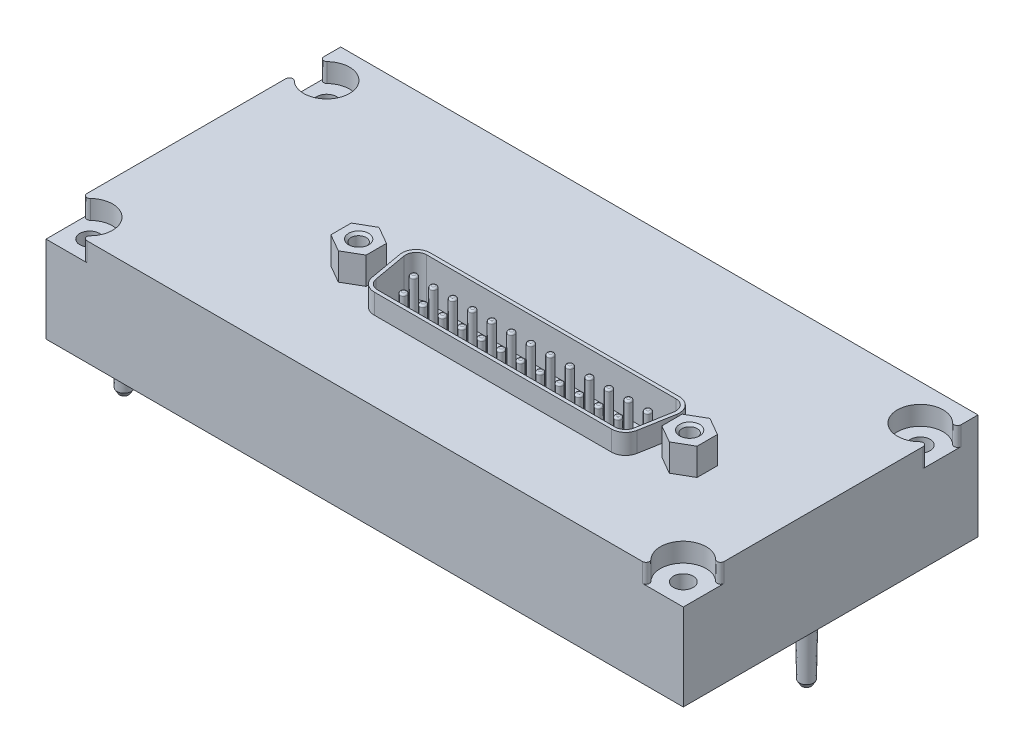
SolidWorks part; units mm, degrees
ref_plane "Ebene vorne" through (0, 0, 0) normal (0, 0, 1) x (1, 0, 0)
ref_plane "Ebene oben" through (0, 0, 0) normal (0, 1, 0) x (1, 0, 0)
ref_plane "Ebene rechts" through (0, 0, 0) normal (1, 0, 0) x (0, 0, -1)
sketch "Skizze1" plane through (0, 0, 0) normal (0, 1, 0) x (1, 0, 0)
  line L0 (-34.25, 15.25) -> (-34.25, -26.6)
  line L1 (-34.25, -26.6) -> (56.25, -26.6)
  line L2 (56.25, -26.6) -> (56.25, 15.25)
  line L3 (56.25, 15.25) -> (-34.25, 15.25)
  circle A0 centre (53.15, -23.5) radius 1.4
  circle A1 centre (53.15, 10.15) radius 1.4
  circle A2 centre (-31.15, -23.5) radius 1.4
  circle A3 centre (-31.15, 10.15) radius 1.4
extrude "Aufsatz-Linear austragen1" add sketch "Skizze1" along normal blind 15
ref_plane "Ebene1" through (0, 15, 0) normal (0, 1, 0) x (1, 0, 0)
sketch "Skizze2" plane through (0, 15, 0) normal (0, 1, 0) x (1, 0, 0)
  line L0 (-45, 30) -> (-45, -40)
  line L1 (-45, -40) -> (65, -40)
  line L2 (65, -40) -> (65, 30)
  line L3 (65, 30) -> (-45, 30)
  line L4 (-34.25, 7.4477) -> (-34.25, -20.7977)
  line L5 (-28.4477, -26.6) -> (50.4477, -26.6)
  line L6 (56.25, -20.7977) -> (56.25, 7.4477)
  line L7 (56.25, 12.8523) -> (56.25, 15.25)
  line L8 (56.25, 15.25) -> (-34.25, 15.25)
  line L9 (-34.25, 15.25) -> (-34.25, 12.8523)
  arc A0 (-34.25, 12.8523) -> (-33.4033, 12.492) centre (-33.75, 12.8523) ccw
  arc A1 (-33.4033, 12.492) -> (-33.4033, 7.808) centre (-31.15, 10.15) cw
  arc A2 (-33.4033, 7.808) -> (-34.25, 7.4477) centre (-33.75, 7.4477) ccw
  arc A3 (-34.25, -20.7977) -> (-33.4033, -21.158) centre (-33.75, -20.7977) ccw
  arc A4 (-33.4033, -21.158) -> (-28.808, -25.7533) centre (-31.15, -23.5) cw
  arc A5 (-28.808, -25.7533) -> (-28.4477, -26.6) centre (-28.4477, -26.1) ccw
  arc A6 (50.4477, -26.6) -> (50.808, -25.7533) centre (50.4477, -26.1) ccw
  arc A7 (50.808, -25.7533) -> (55.4033, -21.158) centre (53.15, -23.5) cw
  arc A8 (55.4033, -21.158) -> (56.25, -20.7977) centre (55.75, -20.7977) ccw
  arc A9 (56.25, 7.4477) -> (55.4033, 7.808) centre (55.75, 7.4477) ccw
  arc A10 (55.4033, 7.808) -> (55.4033, 12.492) centre (53.15, 10.15) cw
  arc A11 (55.4033, 12.492) -> (56.25, 12.8523) centre (55.75, 12.8523) ccw
extrude "Schnitt-Linear austragen1" cut sketch "Skizze2" against normal blind 2.7
ref_plane "Ebene2" through (0, 0, 6) normal (0, 0, 1) x (1, 0, 0)
sketch "Skizze3" plane through (0, 0, 6) normal (0, 0, 1) x (1, 0, 0)
  line L0 (53.15, 0) -> (54.3, 0)
  line L1 (54.3, 0) -> (54.15, -8.4)
  line L2 (54.15, -8.4) -> (53.8, -9)
  line L3 (53.8, -9) -> (53.15, -9)
  line L4 (53.15, -9) -> (53.15, 0)
  line L5 (53.15, -9) -> (53.15, 0) construction
revolve "Rotation1" add sketch "Skizze3" angle 360 about L5 reverse direction yes
ref_plane "Ebene3" through (0, 0, -5.25) normal (0, 0, 1) x (1, 0, 0)
sketch "Skizze4" plane through (0, 0, -5.25) normal (0, 0, 1) x (1, 0, 0)
  line L0 (-31.15, 0) -> (-30, 0)
  line L1 (-30, 0) -> (-30.15, -8.4)
  line L2 (-30.15, -8.4) -> (-30.5, -9)
  line L3 (-30.5, -9) -> (-31.15, -9)
  line L4 (-31.15, -9) -> (-31.15, 0)
  line L5 (-31.15, -9) -> (-31.15, 0) construction
revolve "Rotation2" add sketch "Skizze4" angle 360 about L5 reverse direction yes
ref_plane "Ebene4" through (0, 0, 18.6) normal (0, 0, 1) x (1, 0, 0)
sketch "Skizze5" plane through (0, 0, 18.6) normal (0, 0, 1) x (1, 0, 0)
  line L0 (-31.15, 0) -> (-30, 0)
  line L1 (-30, 0) -> (-30.15, -8.4)
  line L2 (-30.15, -8.4) -> (-30.5, -9)
  line L3 (-30.5, -9) -> (-31.15, -9)
  line L4 (-31.15, -9) -> (-31.15, 0)
  line L5 (-31.15, -9) -> (-31.15, 0) construction
revolve "Rotation3" add sketch "Skizze5" angle 360 about L5 reverse direction yes
sketch "Skizze6" plane through (0, 15, 0) normal (0, 1, 0) x (1, 0, 0)
  line L0 (39, -12.3934) -> (41.5, -13.8368)
  line L1 (41.5, -13.8368) -> (44, -12.3934)
  line L2 (44, -12.3934) -> (44, -9.5066)
  line L3 (44, -9.5066) -> (41.5, -8.0632)
  line L4 (41.5, -8.0632) -> (39, -9.5066)
  line L5 (39, -9.5066) -> (39, -12.3934)
extrude "Aufsatz-Linear austragen2" add sketch "Skizze6" along normal blind 3.85
sketch "Skizze7" plane through (0, 15, 0) normal (0, 1, 0) x (1, 0, 0)
  line L0 (-8, -12.3934) -> (-5.5, -13.8368)
  line L1 (-5.5, -13.8368) -> (-3, -12.3934)
  line L2 (-3, -12.3934) -> (-3, -9.5066)
  line L3 (-3, -9.5066) -> (-5.5, -8.0632)
  line L4 (-5.5, -8.0632) -> (-8, -9.5066)
  line L5 (-8, -9.5066) -> (-8, -12.3934)
extrude "Aufsatz-Linear austragen3" add sketch "Skizze7" along normal blind 3.85
sketch "Skizze8" plane through (0, 15, 0) normal (0, 1, 0) x (1, 0, 0)
  line L0 (-1.2096, -8.8105) -> (-0.3632, -13.6105)
  line L1 (1.114, -14.85) -> (34.806, -14.85)
  line L2 (36.2832, -13.6105) -> (37.1296, -8.8105)
  line L3 (35.6524, -7.05) -> (0.2676, -7.05)
  arc A0 (0.2676, -7.05) -> (-1.2096, -8.8105) centre (0.2676, -8.55) ccw
  arc A1 (-0.3632, -13.6105) -> (1.114, -14.85) centre (1.114, -13.35) ccw
  arc A2 (34.806, -14.85) -> (36.2832, -13.6105) centre (34.806, -13.35) ccw
  arc A3 (37.1296, -8.8105) -> (35.6524, -7.05) centre (35.6524, -8.55) ccw
extrude "Schnitt-Linear austragen2" cut sketch "Skizze8" against normal blind 3
sketch "Skizze9" plane through (0, 15, 0) normal (0, 1, 0) x (1, 0, 0)
  line L0 (-1.702, -8.8973) -> (-0.8556, -13.6973)
  line L1 (1.114, -15.35) -> (34.806, -15.35)
  line L2 (36.7756, -13.6973) -> (37.622, -8.8973)
  line L3 (35.6524, -6.55) -> (0.2676, -6.55)
  line L4 (-1.2096, -8.8105) -> (-0.3632, -13.6105)
  line L5 (1.114, -14.85) -> (34.806, -14.85)
  line L6 (36.2832, -13.6105) -> (37.1296, -8.8105)
  line L7 (35.6524, -7.05) -> (0.2676, -7.05)
  arc A0 (0.2676, -6.55) -> (-1.702, -8.8973) centre (0.2676, -8.55) ccw
  arc A1 (-0.8556, -13.6973) -> (1.114, -15.35) centre (1.114, -13.35) ccw
  arc A2 (34.806, -15.35) -> (36.7756, -13.6973) centre (34.806, -13.35) ccw
  arc A3 (37.622, -8.8973) -> (35.6524, -6.55) centre (35.6524, -8.55) ccw
  arc A4 (0.2676, -7.05) -> (-1.2096, -8.8105) centre (0.2676, -8.55) ccw
  arc A5 (-0.3632, -13.6105) -> (1.114, -14.85) centre (1.114, -13.35) ccw
  arc A6 (34.806, -14.85) -> (36.2832, -13.6105) centre (34.806, -13.35) ccw
  arc A7 (37.1296, -8.8105) -> (35.6524, -7.05) centre (35.6524, -8.55) ccw
extrude "Aufsatz-Linear austragen4" add sketch "Skizze9" along normal blind 2.84
ref_plane "Ebene5" through (0, 0, 10.95) normal (0, 0, 1) x (1, 0, 0)
sketch "Skizze10" plane through (0, 0, 10.95) normal (0, 0, 1) x (1, 0, 0)
  line L0 (41.5, 18.85) -> (42.9224, 18.85)
  line L1 (42.9224, 18.85) -> (42.5782, 18.5058)
  line L2 (42.5782, 18.5058) -> (42.5782, 14.4725)
  line L3 (42.5782, 14.4725) -> (41.5, 13.85)
  line L4 (41.5, 13.85) -> (41.5, 18.85)
  line L5 (41.5, 13.85) -> (41.5, 18.85) construction
revolve "Schnitt-Rotation1" cut sketch "Skizze10" angle 360 about L5 reverse direction yes
cosmetic thread "Gewindedarstellung1" parameters "D1"=3.4, "D2"=2.8448
sketch "Skizze11" plane through (0, 0, 10.95) normal (0, 0, 1) x (1, 0, 0)
  line L0 (-5.5, 18.85) -> (-4.0776, 18.85)
  line L1 (-4.0776, 18.85) -> (-4.4218, 18.5058)
  line L2 (-4.4218, 18.5058) -> (-4.4218, 14.4725)
  line L3 (-4.4218, 14.4725) -> (-5.5, 13.85)
  line L4 (-5.5, 13.85) -> (-5.5, 18.85)
  line L5 (-5.5, 13.85) -> (-5.5, 18.85) construction
revolve "Schnitt-Rotation2" cut sketch "Skizze11" angle 360 about L5 reverse direction yes
cosmetic thread "Gewindedarstellung2" parameters "D1"=3.4, "D2"=2.8448
ref_plane "Ebene6" through (0, 0, 12.37) normal (0, 0, 1) x (1, 0, 0)
sketch "Skizze12" plane through (0, 0, 12.37) normal (0, 0, 1) x (1, 0, 0)
  line L0 (2.305, 17) -> (2.53, 17)
  line L1 (2.78, 16.75) -> (2.78, 12)
  line L2 (2.78, 12) -> (2.305, 12)
  line L3 (2.305, 12) -> (2.305, 17)
  line L4 (2.305, 12) -> (2.305, 17) construction
  arc A0 (2.53, 17) -> (2.78, 16.75) centre (2.53, 16.75) cw
revolve "Rotation4" add sketch "Skizze12" angle 360 about L4 reverse direction yes
ref_plane "Ebene7" through (0, 12, 0) normal (0, 1, 0) x (1, 0, 0)
sketch "Skizze13" plane through (0, 12, 0) normal (0, 1, 0) x (1, 0, 0)
  line L0 (2.305, -12.37) -> (32.775, -12.37)
pattern_linear "Lineares Muster1" count 12 spacing 2.77 along (1, 0, 0) of "Rotation4"
ref_plane "Ebene8" through (0, 0, 9.53) normal (0, 0, 1) x (1, 0, 0)
sketch "Skizze14" plane through (0, 0, 9.53) normal (0, 0, 1) x (1, 0, 0)
  line L0 (0.92, 17) -> (1.145, 17)
  line L1 (1.395, 16.75) -> (1.395, 12)
  line L2 (1.395, 12) -> (0.92, 12)
  line L3 (0.92, 12) -> (0.92, 17)
  line L4 (0.92, 12) -> (0.92, 17) construction
  arc A0 (1.145, 17) -> (1.395, 16.75) centre (1.145, 16.75) cw
revolve "Rotation5" add sketch "Skizze14" angle 360 about L4 reverse direction yes
sketch "Skizze15" plane through (0, 12, 0) normal (0, 1, 0) x (1, 0, 0)
  line L0 (0.92, -9.53) -> (34.16, -9.53)
pattern_linear "Lineares Muster2" count 13 spacing 2.77 along (1, 0, 0) of "Rotation5"
ref_plane "Ebene9" through (0, 0, 10.95) normal (0, 0, 1) x (1, 0, 0)
ref_plane "Ebene10" through (0, 12.3, 0) normal (0, 1, 0) x (1, 0, 0)
ref_plane "Ebene11" through (0, 18.85, 0) normal (0, 1, 0) x (1, 0, 0)
ref_plane "ANBAU XY" through (0, 0, 0) normal (0, 1, 0) x (1, 0, 0)
ref_plane "ANBAU XZ" through (0, 0, 6) normal (0, 0, -1) x (-1, 0, 0)
ref_plane "ANBAU YZ" through (53.15, 0, 0) normal (-1, 0, 0) x (0, 0, 1)
ref_axis "ANBAU X" through (80.9, 0, 6) along (-1, 0, 0)
ref_axis "ANBAU Y" through (53.15, 0, -50) along (0, 0, 1)
ref_axis "ANBAU Z" through (53.15, 50, 6) along (0, -1, 0)
sketch3d "ANBAU"
  point P0 (53.15, 0, 6)
ref_plane "EZ XY" through (0, 18.85, 0) normal (0, -1, 0) x (-1, 0, 0)
ref_plane "EZ XZ" through (0, 0, 10.95) normal (0, 0, -1) x (-1, 0, 0)
ref_plane "EZ YZ" through (-5.5, 0, 0) normal (1, 0, 0) x (0, 0, -1)
ref_axis "EZ X" through (-80.9, 18.85, 10.95) along (1, 0, 0)
ref_axis "EZ Y" through (-5.5, 18.85, -50) along (0, 0, 1)
ref_axis "EZ Z" through (-5.5, -50, 10.95) along (0, 1, 0)
sketch3d "EZ"
  point P0 (-5.5, 18.85, 10.95)
ref_plane "SCREW 1 XY" through (0, 12.3, 0) normal (0, -1, 0) x (-1, 0, 0)
ref_plane "SCREW 1 XZ" through (0, 0, 23.5) normal (0, 0, -1) x (-1, 0, 0)
ref_plane "SCREW 1 YZ" through (-31.15, 0, 0) normal (1, 0, 0) x (0, 0, -1)
ref_axis "SCREW 1 X" through (-80.9, 12.3, 23.5) along (1, 0, 0)
ref_axis "SCREW 1 Y" through (-31.15, 12.3, -50) along (0, 0, 1)
ref_axis "SCREW 1 Z" through (-31.15, -50, 23.5) along (0, 1, 0)
sketch3d "SCREW 1"
  point P0 (-31.15, 12.3, 23.5)
ref_plane "SCREW 2 XY" through (0, 12.3, 0) normal (0, -1, 0) x (-1, 0, 0)
ref_plane "SCREW 2 XZ" through (0, 0, 23.5) normal (0, 0, -1) x (-1, 0, 0)
ref_plane "SCREW 2 YZ" through (53.15, 0, 0) normal (1, 0, 0) x (0, 0, -1)
ref_axis "SCREW 2 X" through (-80.9, 12.3, 23.5) along (1, 0, 0)
ref_axis "SCREW 2 Y" through (53.15, 12.3, -50) along (0, 0, 1)
ref_axis "SCREW 2 Z" through (53.15, -50, 23.5) along (0, 1, 0)
sketch3d "SCREW 2"
  point P0 (53.15, 12.3, 23.5)
ref_plane "SCREW 3 XY" through (0, 12.3, 0) normal (0, -1, 0) x (-1, 0, 0)
ref_plane "SCREW 3 XZ" through (0, 0, -10.15) normal (0, 0, -1) x (-1, 0, 0)
ref_plane "SCREW 3 YZ" through (-31.15, 0, 0) normal (1, 0, 0) x (0, 0, -1)
ref_axis "SCREW 3 X" through (-80.9, 12.3, -10.15) along (1, 0, 0)
ref_axis "SCREW 3 Y" through (-31.15, 12.3, -50) along (0, 0, 1)
ref_axis "SCREW 3 Z" through (-31.15, -50, -10.15) along (0, 1, 0)
sketch3d "SCREW 3"
  point P0 (-31.15, 12.3, -10.15)
ref_plane "SCREW 4 XY" through (0, 12.3, 0) normal (0, -1, 0) x (-1, 0, 0)
ref_plane "SCREW 4 XZ" through (0, 0, -10.15) normal (0, 0, -1) x (-1, 0, 0)
ref_plane "SCREW 4 YZ" through (53.15, 0, 0) normal (1, 0, 0) x (0, 0, -1)
ref_axis "SCREW 4 X" through (-80.9, 12.3, -10.15) along (1, 0, 0)
ref_axis "SCREW 4 Y" through (53.15, 12.3, -50) along (0, 0, 1)
ref_axis "SCREW 4 Z" through (53.15, -50, -10.15) along (0, 1, 0)
sketch3d "SCREW 4"
  point P0 (53.15, 12.3, -10.15)
